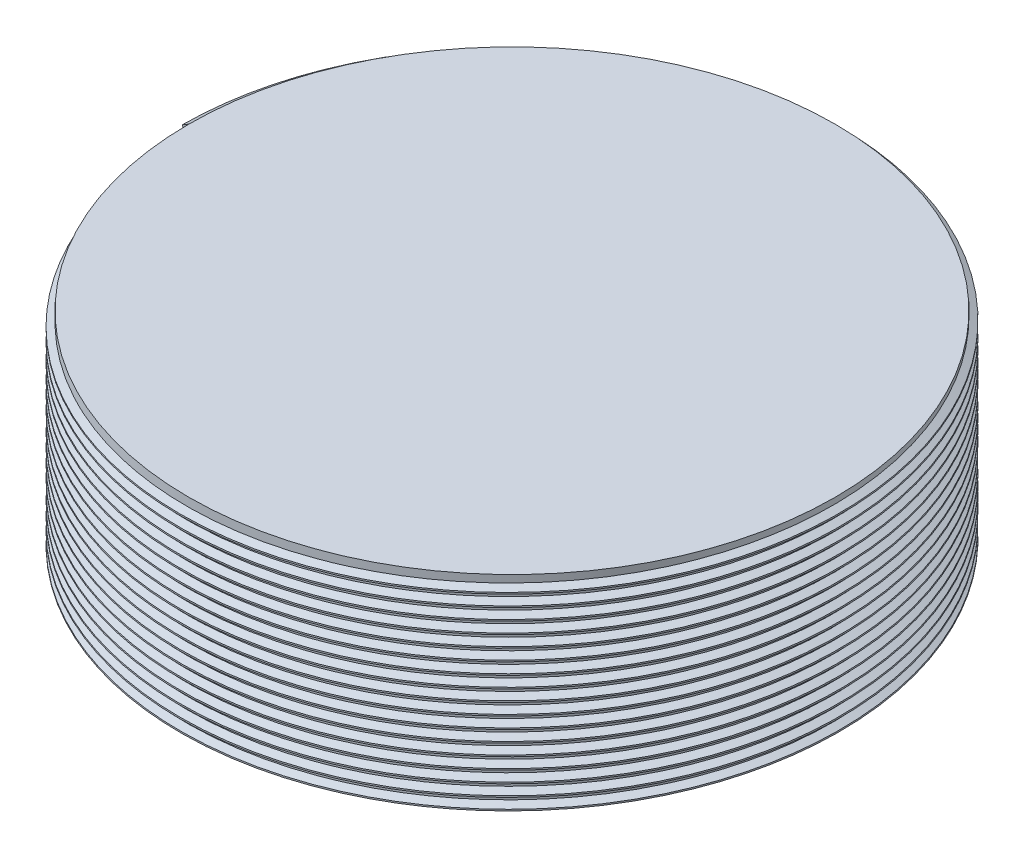
SolidWorks part; units mm, degrees
ref_plane "Front Plane" through (0, 0, 0) normal (0, 0, 1) x (1, 0, 0)
ref_plane "Top Plane" through (0, 0, 0) normal (0, 1, 0) x (1, 0, 0)
ref_plane "Right Plane" through (0, 0, 0) normal (1, 0, 0) x (0, 0, -1)
sketch "Sketch1" plane through (0, 0, 0) normal (0, 1, 0) x (1, 0, 0)
  circle A0 centre (0, 0) radius 20.65
  dimension "D1" = 41.3
extrude "Boss-Extrude1" add sketch "Sketch1" along normal blind 12.7
thread "MinColWidth_OnTracking1" pitch 0.75 method extrude profile "HeaderRowsCount1" start angle 0, offset 0, length 13, pitch 0.75, diameter 41.3
ref_plane "Plane1" through (-20.65, 12.7, 0) normal (0, 0, 1) x (-1, 0, 0)
sketch "HeaderRowsCount1" plane through (-20.65, 12.7, 0) normal (0, 0, 1) x (-1, 0, 0)
  line L0 (0, 0) -> (0, 0.75) construction
  line L1 (0, 0) -> (0.4059, 0.2344)
  line L2 (0.4059, 0.2344) -> (0.4059, 0.3281)
  line L3 (0.4059, 0.3281) -> (0, 0.5625)
  line L4 (0.4059, 0.2813) -> (0, 0.2813) construction
  line L11 (0, 0) -> (0, 0.5625)
  point P2 (0, 0)
  dimension "Pitch" = 0.75
  dimension "Profile_Angle" = 60
  dimension "Profile_Land" = 0.0938
  dimension "Profile_Height" = 0.4059
